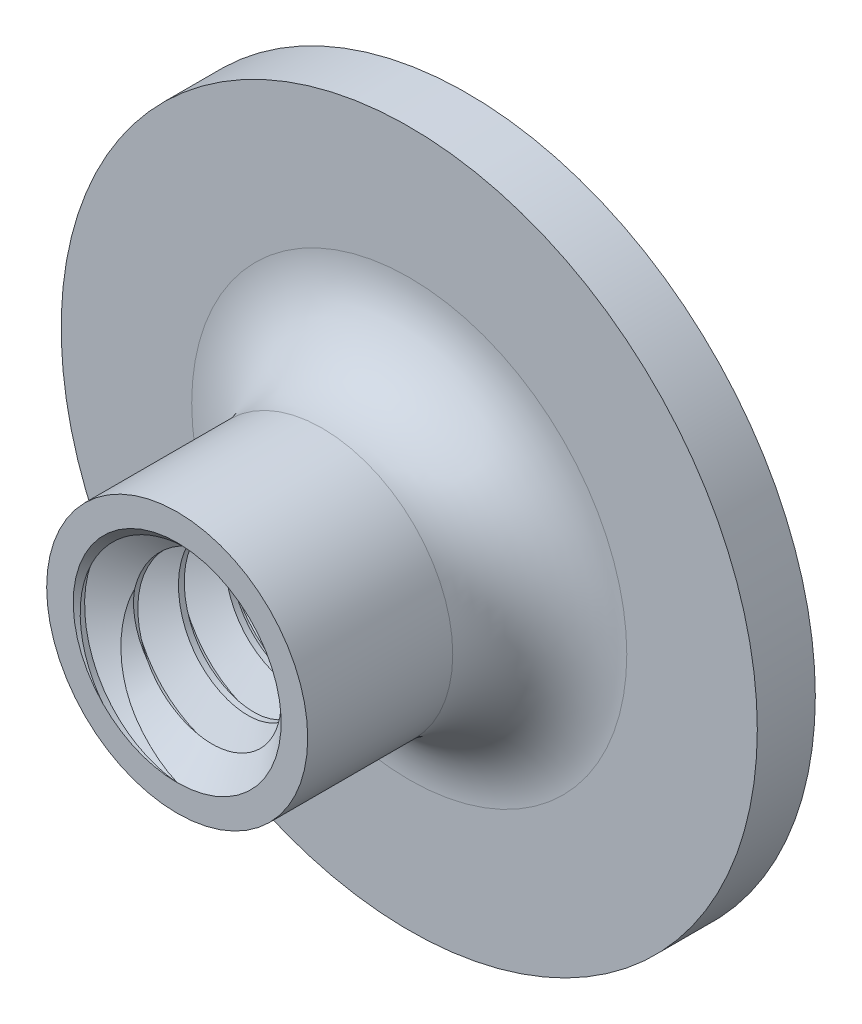
SolidWorks part; units mm, degrees
ref_plane "Front Plane" through (0, 0, 0) normal (0, 0, 1) x (1, 0, 0)
ref_plane "Top Plane" through (0, 0, 0) normal (0, 1, 0) x (1, 0, 0)
ref_plane "Right Plane" through (0, 0, 0) normal (1, 0, 0) x (0, 0, -1)
sketch "Sketch1" plane through (0, 0, 0) normal (0, 0, 1) x (1, 0, 0)
  circle A0 centre (0, 0) radius 4.7625
  circle A1 centre (0, 0) radius 1.4224
  dimension "D1" = 2.8448
  dimension "base dia" = 9.525
extrude "Extrude1" add sketch "Sketch1" along normal blind 0.7937
sketch "Sketch2" plane through (0, 0, 0.7937) normal (0, 0, 1) x (1, 0, 0)
  circle A0 centre (0, 0) radius 1.7859
  circle A1 centre (0, 0) radius 1.4224
  dimension "OD" = 2.8448
  dimension "Barrel Dia" = 3.5719
extrude "Extrude2" add sketch "Sketch2" along normal blind 3.175
sketch "Sketch3" plane through (0, 0, 0) normal (0, 0, -1) x (-1, 0, 0)
  circle A0 centre (0, 0) radius 1.4224 construction
  circle A1 centre (0, 0) radius 1.4224
curve "Helix/Spiral1" pitch 0.635 height 6.35 radius 1.4224 centre (0, 0, 0) axis (0, 0, 1) start towards (-1, 0, 0) parameters "pitch"=0.635
sketch "Sketch4" plane through (0, 0, 0) normal (0, 1, 0) x (1, 0, 0)
  line L0 (-1.4224, 0.5556) -> (-1.4224, 0)
  line L1 (-1.4224, 0) -> (-1.01, 0.2381)
  line L2 (-1.01, 0.2381) -> (-1.01, 0.3175)
  line L3 (-1.01, 0.3175) -> (-1.4224, 0.5556)
  line L4 (-1.01, 0.2778) -> (-1.4224, 0.2778) construction
  line L5 (-1.2162, 0.1191) -> (-1.2162, 0.4366) construction
  dimension "D1" = 0.0794
  dimension "D2" = 0.3175
  dimension "D3" = 60
sweep "Sweep1" add profiles "Sketch4" path "Helix/Spiral1"
sketch "Sketch5" plane through (0, 0, 0) normal (0, 0, -1) x (-1, 0, 0)
  circle A1 centre (0, 0) radius 4.7625
  circle A2 centre (0, 0) radius 4.7625
  dimension "D1" = 0
extrude "Cut-Extrude1" cut sketch "Sketch5" along normal through all
sketch "Sketch6" plane through (0, 0, 0) normal (0, 0, -1) x (-1, 0, 0)
  circle A0 centre (0, 0) radius 1.4224 construction
  circle A1 centre (0, 0) radius 1.4224 construction
  circle A2 centre (0, 0) radius 1.4732
  dimension "D1" = 0.0508
extrude "Cut-Extrude2" cut sketch "Sketch6" against normal through all draft 45
sketch "Sketch7" plane through (0, 0, 3.9688) normal (0, 0, 1) x (1, 0, 0)
  circle A1 centre (0, 0) radius 1.7859
  circle A2 centre (0, 0) radius 1.7859
  dimension "D1" = 0
extrude "Cut-Extrude3" cut sketch "Sketch7" along normal through all
sketch "Sketch8" plane through (0, 0, 3.9688) normal (0, 0, 1) x (1, 0, 0)
  circle A0 centre (0, 0) radius 1.4224 construction
  circle A1 centre (0, 0) radius 1.4224
extrude "Cut-Extrude4" cut sketch "Sketch8" against normal through all draft 45
fillet "Fillet1" radius 1.1906 1 edges at (1.7859, 0, 0.7937)
equation "\"D1@Sketch1\" = \"OD@Sketch2\""
equation "\"D3@Helix/Spiral1\" = \"height@Extrude2\"+.125"
equation "\"D1@Sketch4\" = \"pitch@Helix/Spiral1\"*.125"
equation "\"D2@Sketch4\" = \"pitch@Helix/Spiral1\"*.5"
equation "\"D1@Fillet1\" = \"base thickness@Extrude1\"*1.50"
